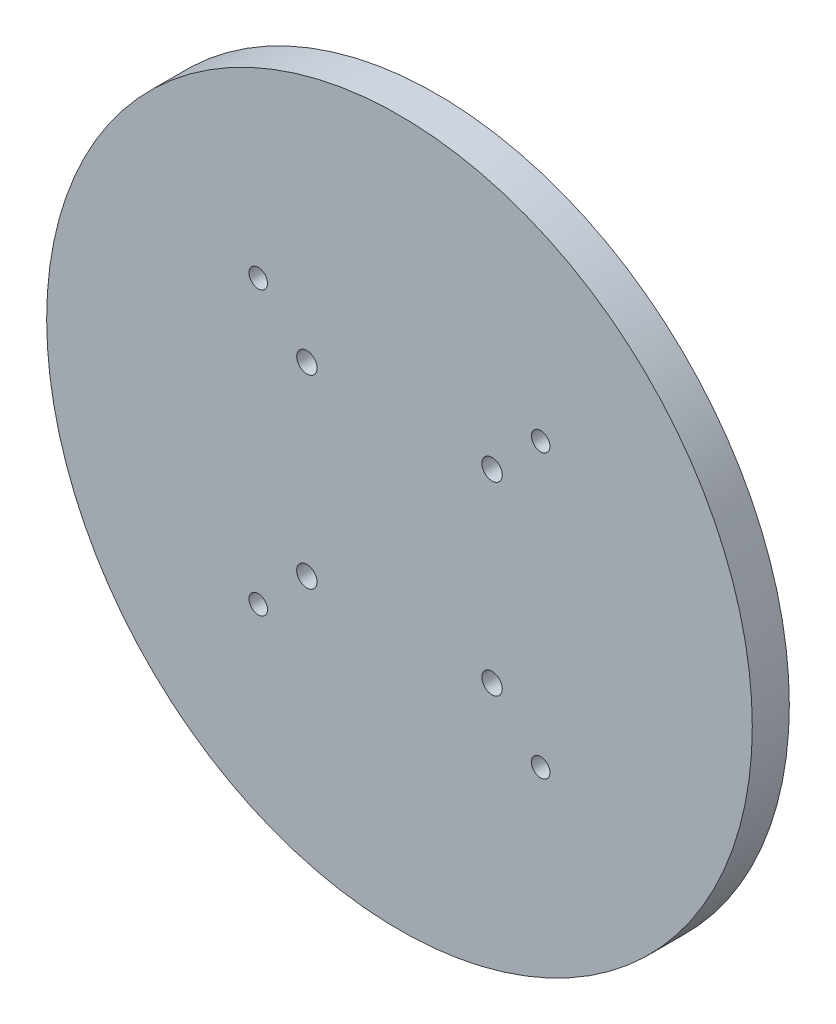
SolidWorks part; units mm, degrees
material "Hexcel AS4C (3000 Filaments)"
ref_plane "Front Plane" through (0, 0, 0) normal (0, 0, 1) x (1, 0, 0)
ref_plane "Top Plane" through (0, 0, 0) normal (0, 1, 0) x (1, 0, 0)
ref_plane "Right Plane" through (0, 0, 0) normal (1, 0, 0) x (0, 0, -1)
sketch "Sketch1" plane through (0, 0, 0) normal (0, 0, 1) x (1, 0, 0)
  circle A0 centre (0, 0) radius 38.1
  dimension "D1" = 76.2
extrude "Boss-Extrude1" add sketch "Sketch1" along normal blind 4 contours A0
sketch "Sketch2" plane through (0, 0, 4) normal (0, 0, 1) x (1, 0, 0)
  circle A0 centre (10, 10) radius 1.1
  circle A1 centre (10, -10) radius 1.1
  circle A2 centre (-10, -10) radius 1.1
  circle A3 centre (-10, 10) radius 1.1
  circle A4 centre (15.25, -15.25) radius 1
  circle A5 centre (-15.25, -15.25) radius 1
  circle A6 centre (-15.25, 15.25) radius 1
  circle A7 centre (15.25, 15.25) radius 1
  point P2 (0, 0)
  point P12 (0, 0)
  point P21 (0, 0)
  dimension "D3" = 2.2
  dimension "D7" = 2
  dimension "D1" = 10
  dimension "D2" = 10
  dimension "D5" = 15.25
  dimension "D6" = 15.25
  dimension "D4" = 4
  dimension "D8" = 4
extrude "Cut-Extrude1" cut sketch "Sketch2" against normal through all
